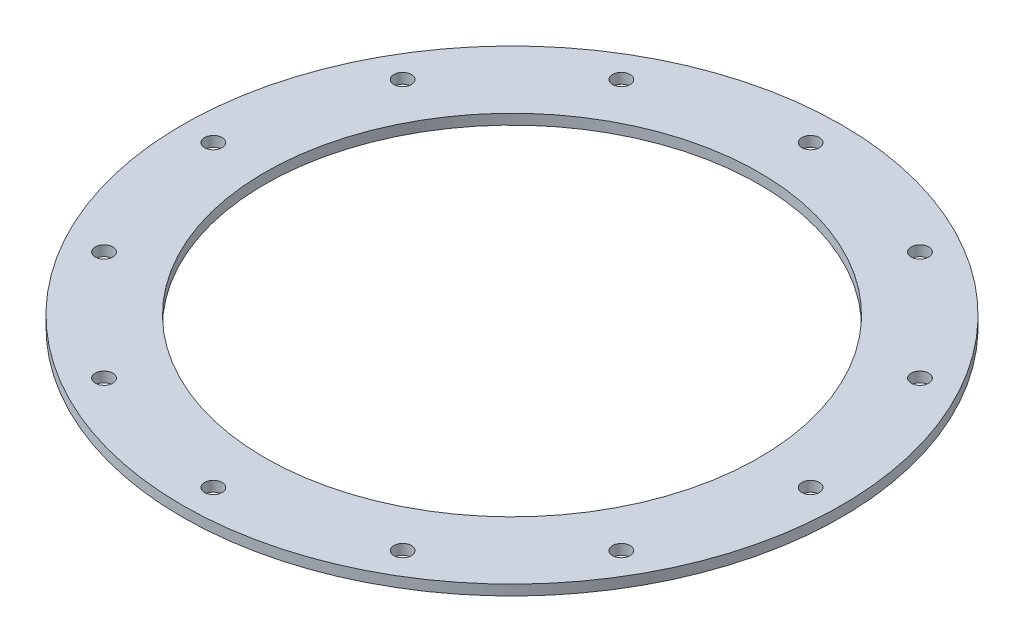
SolidWorks part; units mm, degrees
material "PTFE (general)"
ref_plane "Front Plane" through (0, 0, 0) normal (0, 0, 1) x (1, 0, 0)
ref_plane "Top Plane" through (0, 0, 0) normal (0, 1, 0) x (1, 0, 0)
ref_plane "Right Plane" through (0, 0, 0) normal (1, 0, 0) x (0, 0, -1)
ref_axis "Axis1" through (0, 55, 0) along (0, -1, 0)
sketch "Sketch1" plane through (0, 0, 0) normal (0, 0, 1) x (1, 0, 0)
  line L0 (-38.1, 0) -> (0, 0) construction
  line L1 (-38.1, 0) -> (-50.8, 0)
  line L2 (-38.1, 0) -> (-38.1, 1.5875)
  line L3 (-38.1, 1.5875) -> (-50.8, 1.5875)
  line L4 (-50.8, 0) -> (-50.8, 1.5875)
  line L7 (0, 1.5875) -> (-38.1, 1.5875) construction
  point P12 (-50.8, 0)
  point P18 (-38.1, 1.5875)
revolve "Main" add sketch "Sketch1" angle 360 about axis through (0, 55, 0) along (0, -1, 0)
sketch "Hole Location" plane through (0, 0, 0) normal (0, 1, 0) x (1, 0, 0)
  line L0 (0, 0) -> (-46.0375, 0) construction
  circle A0 centre (0, 0) radius 46.0375 construction
  dimension "D1" = 92.075
hole_wizard "#36 (0.1065) Diameter Hole1" positions "Sketch3" profile "Sketch5" hole size "#36" standard "ANSI Inch" end condition through all
sketch "Sketch3" plane through (0, 0, 0) normal (0, -1, 0) x (-1, 0, 0)
  point P0 (46.0375, 0)
sketch "Sketch5" plane through (-46.0375, 0, 0) normal (1, 0, 0) x (0, 0, -1)
  line L0 (0, 0) -> (0, 1.5875)
  line L1 (0, 1.5875) -> (1.3525, 1.5875)
  line L2 (1.3525, 1.5875) -> (1.3525, 0)
  line L5 (1.3525, 0) -> (0, 0)
  line L11 (0, -6.35) -> (0, 107.95) construction
  dimension "Thru Hole Dia." = 2.7051
  dimension "Thru Hole Depth" = 1.5875
pattern_circular "Screw Passthroughs" count 12 over 360 about axis through (0, 55, 0) along (0, -1, 0) of "#36 (0.1065) Diameter Hole1"
equation "\"D1@Hole Location\"=\"TANK DIAMETER@Cryo Tank.Assembly\"+\"GASKET SEAT THICKNESS@Cryo Tank.Assembly\"+\"LINER THICKNESS@Cryo Tank.Assembly\""
